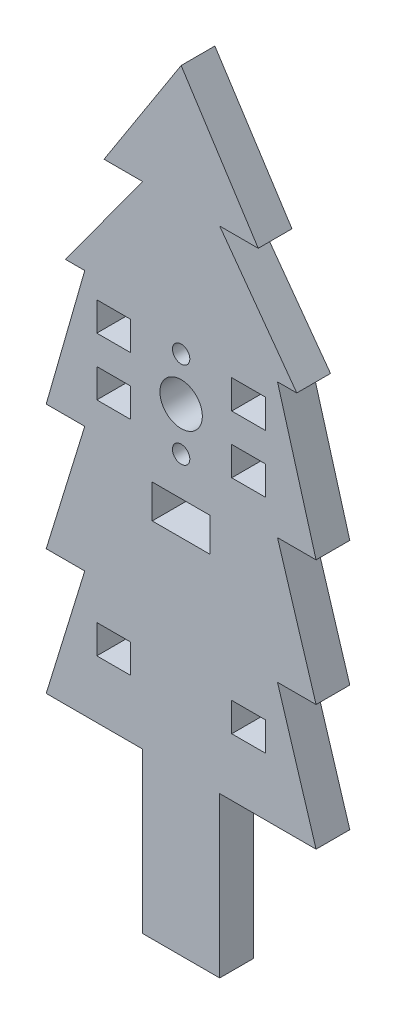
SolidWorks part; units mm, degrees
ref_plane "Ebene vorne (XY)" through (0, 0, 0) normal (0, 0, 1) x (1, 0, 0)
ref_plane "Ebene oben  (XZ)" through (0, 0, 0) normal (0, 1, 0) x (1, 0, 0)
ref_plane "Ebene rechts  (YZ)" through (0, 0, 0) normal (1, 0, 0) x (0, 0, -1)
ref_axis "x-Achse" through (-15.4, 0, 0) along (1, 0, 0)
ref_axis "y-Achse" through (0, 34.4272, 0) along (0, -1, 0)
ref_axis "z-Achse" through (0, 0, -0.175) along (0, 0, 1)
sketch "Profile_Laser_profile_3p5" plane through (0, 0, 0) normal (0, 0, 1) x (1, 0, 0)
  line L0 (0, 30.4272) -> (8, 18)
  line L1 (8, 18) -> (4, 18)
  line L2 (4, 18) -> (12, 7)
  line L3 (12, 7) -> (10, 7)
  line L4 (10, 7) -> (14, -7)
  line L5 (14, -7) -> (10, -7)
  line L6 (10, -7) -> (14, -20)
  line L7 (14, -20) -> (10, -20)
  line L8 (10, -20) -> (14, -33)
  line L9 (14, -33) -> (4, -33)
  line L10 (4, -33) -> (4, -49.5728)
  line L11 (4, -49.5728) -> (-4, -49.5728)
  line L12 (-4, -49.5728) -> (-4, -33)
  line L13 (-4, -33) -> (-14, -33)
  line L14 (-14, -33) -> (-10, -20)
  line L15 (-10, -20) -> (-14, -20)
  line L16 (-14, -20) -> (-10, -7)
  line L17 (-10, -7) -> (-14, -7)
  line L18 (-14, -7) -> (-10, 7)
  line L19 (-10, 7) -> (-12, 7)
  line L20 (-12, 7) -> (-4, 18)
  line L21 (-4, 18) -> (-8, 18)
  line L22 (-8, 18) -> (0, 30.4272)
  line L23 (-8.75, 2) -> (-5.25, 2)
  line L24 (-5.25, 2) -> (-5.25, 5)
  line L25 (-5.25, 5) -> (-8.75, 5)
  line L26 (-8.75, 5) -> (-8.75, 2)
  line L27 (-8.75, -4) -> (-5.25, -4)
  line L28 (-5.25, -4) -> (-5.25, -1)
  line L29 (-5.25, -1) -> (-8.75, -1)
  line L30 (-8.75, -1) -> (-8.75, -4)
  line L31 (-8.75, -27) -> (-5.25, -27)
  line L32 (-5.25, -27) -> (-5.25, -24)
  line L33 (-5.25, -24) -> (-8.75, -24)
  line L34 (-8.75, -24) -> (-8.75, -27)
  line L35 (5.25, 2) -> (8.75, 2)
  line L36 (8.75, 2) -> (8.75, 5)
  line L37 (8.75, 5) -> (5.25, 5)
  line L38 (5.25, 5) -> (5.25, 2)
  line L39 (5.25, -4) -> (8.75, -4)
  line L40 (8.75, -4) -> (8.75, -1)
  line L41 (8.75, -1) -> (5.25, -1)
  line L42 (5.25, -1) -> (5.25, -4)
  line L43 (5.25, -27) -> (8.75, -27)
  line L44 (8.75, -27) -> (8.75, -24)
  line L45 (8.75, -24) -> (5.25, -24)
  line L46 (5.25, -24) -> (5.25, -27)
  line L47 (-3, -12) -> (3, -12)
  line L48 (3, -12) -> (3, -8.5)
  line L49 (3, -8.5) -> (-3, -8.5)
  line L50 (-3, -8.5) -> (-3, -12)
  circle A0 centre (0, 0) radius 2.2
  circle A1 centre (0, -4.5) radius 0.9
  circle A2 centre (0, 4.5) radius 0.9
extrude "Laser_profile_3p5" add sketch "Profile_Laser_profile_3p5" along normal blind 3.5
